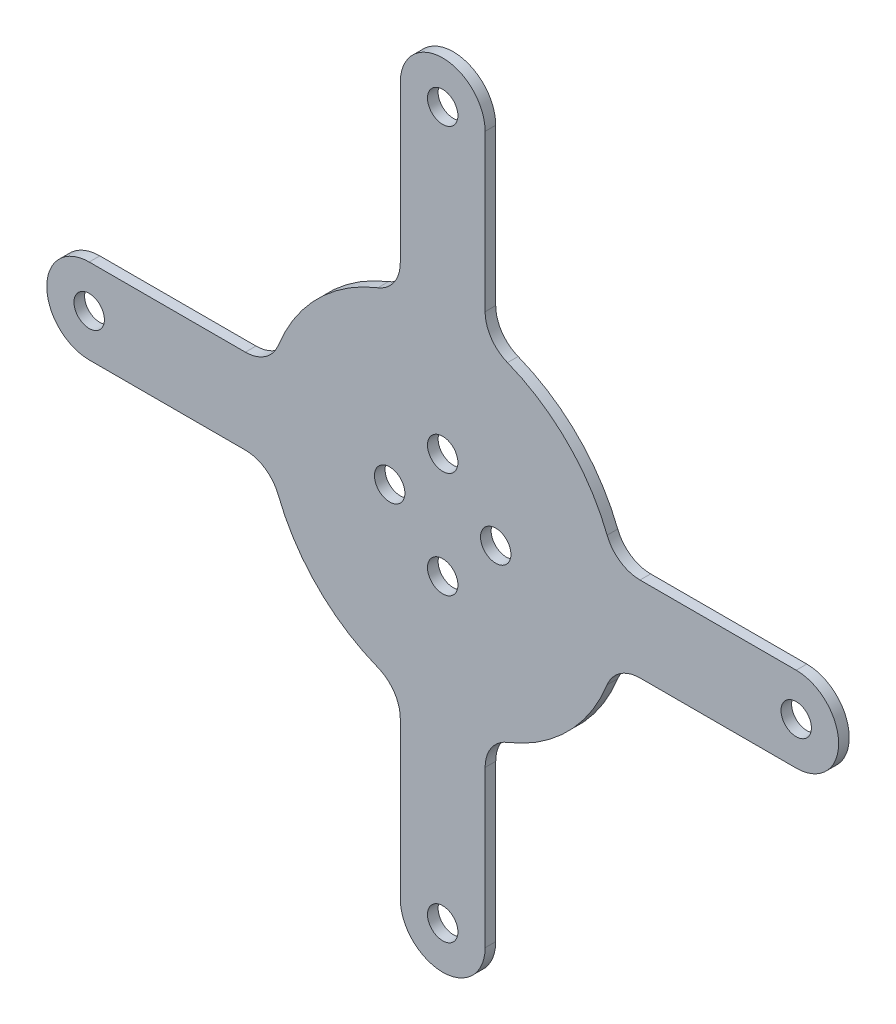
SolidWorks part; units mm, degrees
material "5052-H34"
ref_plane "正面" through (0, 0, 0) normal (0, 0, 1) x (1, 0, 0)
ref_plane "平面" through (0, 0, 0) normal (0, 1, 0) x (1, 0, 0)
ref_plane "右側面" through (0, 0, 0) normal (1, 0, 0) x (0, 0, -1)
sketch "ｽｹｯﾁ1" plane through (0, 0, 0) normal (0, 0, 1) x (1, 0, 0)
  line L0 (0, 0) -> (0, 7.5) construction
  line L1 (0, 0) -> (0, 50) construction
  line L2 (-6, 50) -> (-6, 24.2693)
  line L3 (6, 50) -> (6, 24.2693)
  line L4 (50, -6) -> (24.2693, -6)
  line L5 (50, 6) -> (24.2693, 6)
  line L6 (-6, -50) -> (-6, -24.2693)
  line L7 (6, -50) -> (6, -24.2693)
  line L8 (-50, 6) -> (-24.2693, 6)
  line L9 (-50, -6) -> (-24.2693, -6)
  circle A0 centre (0, 7.5) radius 2.15
  circle A1 centre (0, 50) radius 2.15
  circle A2 centre (50, 0) radius 2.15
  circle A3 centre (7.5, 0) radius 2.15
  circle A4 centre (0, -50) radius 2.15
  circle A5 centre (0, -7.5) radius 2.15
  circle A6 centre (-50, 0) radius 2.15
  circle A7 centre (-7.5, 0) radius 2.15
  arc A8 (-24.2693, -6) -> (-6, -24.2693) centre (0, 0) ccw
  arc A9 (6, 50) -> (-6, 50) centre (0, 50) ccw
  arc A10 (50, -6) -> (50, 6) centre (50, 0) ccw
  arc A11 (-6, -50) -> (6, -50) centre (0, -50) ccw
  arc A12 (-50, 6) -> (-50, -6) centre (-50, 0) ccw
  arc A13 (-24.2693, 6) -> (-24.2693, -6) centre (0, 0) ccw construction
  arc A14 (-6, -24.2693) -> (6, -24.2693) centre (0, 0) ccw construction
  arc A15 (6, -24.2693) -> (24.2693, -6) centre (0, 0) ccw
  arc A16 (24.2693, -6) -> (24.2693, 6) centre (0, 0) ccw construction
  arc A17 (24.2693, 6) -> (6, 24.2693) centre (0, 0) ccw
  arc A18 (0, 25) -> (-6, 24.2693) centre (0, 0) ccw construction
  arc A19 (-6, 24.2693) -> (-24.2693, 6) centre (0, 0) ccw
  arc A20 (6, 24.2693) -> (0, 25) centre (0, 0) ccw construction
  arc A21 (0, 44) -> (6, 50) centre (0, 50) ccw construction
  arc A22 (-6, 50) -> (0, 44) centre (0, 50) ccw construction
  arc A23 (-50, -6) -> (-50, 6) centre (-50, 0) ccw construction
  arc A24 (6, -50) -> (-6, -50) centre (0, -50) ccw construction
  arc A25 (50, 6) -> (50, -6) centre (50, 0) ccw construction
  point P20 (0, 0)
  point P40 (0, 0)
  point P47 (0, 0)
  dimension "D1" = 4.3
  dimension "D2" = 4.3
  dimension "D6" = 50
  dimension "D7" = 12
  dimension "D3" = 50
  dimension "D4" = 4
  dimension "D5" = 15
  dimension "D8" = 4
  dimension "D9" = 4
extrude "ﾎﾞｽ - 押し出し1" add sketch "ｽｹｯﾁ1" along normal blind 1.5
fillet "ﾌｨﾚｯﾄ1" radius 5 8 edges at (-6, 24.2693, 0.75) (-24.2693, 6, 0.75) (-24.2693, -6, 0.75) (-6, -24.2693, 0.75) (6, -24.2693, 0.75) (24.2693, -6, 0.75) (24.2693, 6, 0.75) (6, 24.2693, 0.75)
